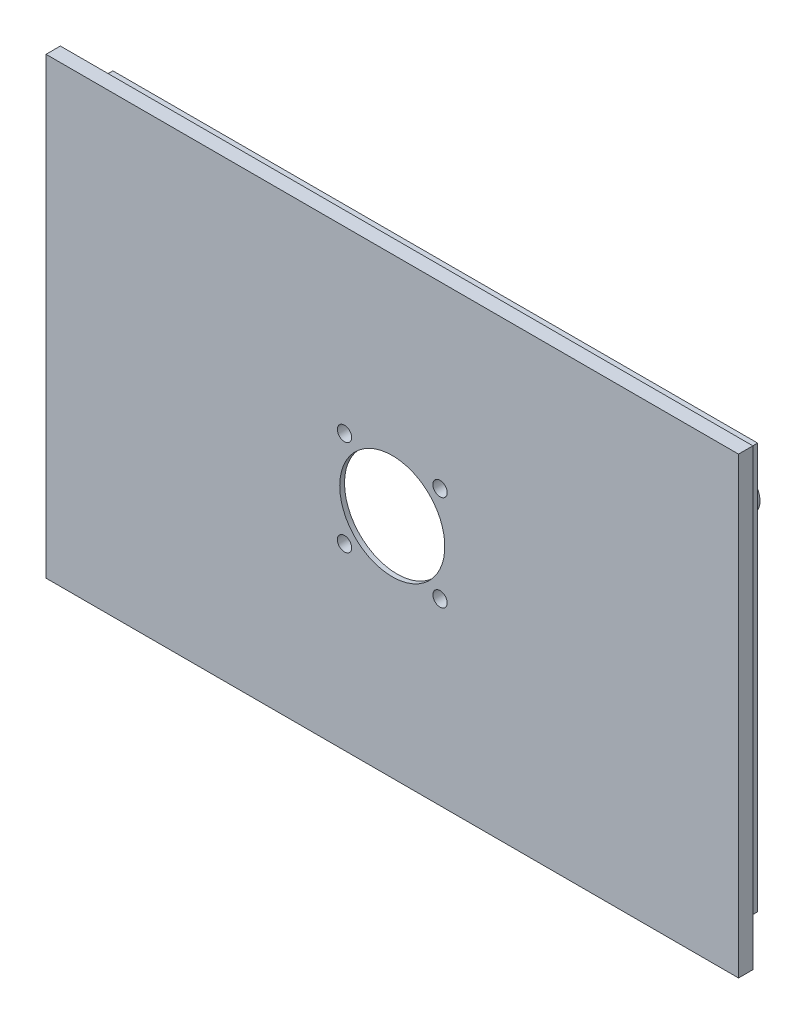
SolidWorks part; units mm, degrees
ref_plane "Plano frontal" through (0, 0, 0) normal (0, 0, 1) x (1, 0, 0)
ref_plane "Plano superior" through (0, 0, 0) normal (0, 1, 0) x (1, 0, 0)
ref_plane "Plano direito" through (0, 0, 0) normal (1, 0, 0) x (0, 0, -1)
sketch "Esboço1" plane through (0, 0, 0) normal (0, 0, 1) x (1, 0, 0)
  line L1 (0, 0) -> (150, 0)
  line L2 (0, 0) -> (0, 100)
  line L3 (0, 100) -> (150, 100)
  line L4 (150, 0) -> (150, 100)
  line L5 (10, 90) -> (140, 90)
  line L6 (10, 90) -> (10, 10)
  line L7 (10, 10) -> (140, 10)
  line L8 (140, 90) -> (140, 10)
  line L9 (7.5, 92.5) -> (142.5, 92.5)
  line L10 (7.5, 92.5) -> (7.5, 7.5)
  line L11 (7.5, 7.5) -> (142.5, 7.5)
  line L12 (142.5, 92.5) -> (142.5, 7.5)
  dimension "D1" = 100
  dimension "D2" = 150
  dimension "D3" = 130
  dimension "D4" = 80
  dimension "D5" = 10
  dimension "D6" = 10
  dimension "D7" = 2.5
  dimension "D8" = 2.5
  dimension "D9" = 2.5
  dimension "D10" = 2.5
extrude "Ressalto-extrusão1" add sketch "Esboço1" along normal blind 3 contours L3 L4 L1 L2
extrude "Ressalto-extrusão2" add sketch "Esboço1<3>" against normal blind 6 contours L12 L9 L10 L11 L5 L8 L7 L6 region at (75, 90.9047, 0)
sketch "Esboço1<3>" plane through (0, 0, 0) normal (0, 0, 1) x (1, 0, 0) same geometry as "Esboço1"
sketch "Esboço2" plane through (0, 0, 0) normal (0, 0, -1) x (-1, 0, 0)
  line L0 (-10, 90) -> (-140, 90) construction
  line L2 (-140, 90) -> (-140, 10) construction
  circle A0 centre (-130, 73.25) radius 4
  circle A1 centre (-32, 76.75) radius 4
  circle A2 centre (-28, 25.75) radius 4
  circle A3 centre (-124, 23.25) radius 4
  dimension "D6" = 50
  dimension "D7" = 8
  dimension "D8" = 8
  dimension "D9" = 8
  dimension "D10" = 8
  dimension "D1" = 98
  dimension "D2" = 3.5
  dimension "D3" = 4
  dimension "D4" = 6
  dimension "D5" = 51
  dimension "D11" = 13.25
  dimension "D12" = 10
extrude "Ressalto-extrusão3" add sketch "Esboço2" along normal blind 15
sketch "Esboço3" plane through (0, 0, -15) normal (0, 0, -1) x (-1, 0, 0)
  circle A0 centre (-130, 73.25) radius 1.75
  circle A1 centre (-32, 76.75) radius 1.75
  circle A2 centre (-28, 25.75) radius 1.75
  circle A3 centre (-124, 23.25) radius 1.75
  dimension "D1" = 3.5
  dimension "D2" = 3.5
  dimension "D3" = 3.5
  dimension "D4" = 3.5
extrude "Corte-extrusão1" cut sketch "Esboço3" against normal blind 8
sketch "Esboço4" plane through (0, 0, 0) normal (0, 0, -1) x (-1, 0, 0)
  line L0 (-75, 10) -> (-75, 100) construction
  line L1 (-68, 83.7797) -> (-82, 83.7797)
  line L2 (-68, 83.7797) -> (-68, 85.7604)
  line L3 (-68, 85.7604) -> (-82, 85.7604)
  line L4 (-82, 83.7797) -> (-82, 85.7604)
  line L5 (-10, 10) -> (-140, 10) construction
  line L6 (0, 100) -> (-150, 100) construction
  dimension "D1" = 7
  dimension "D2" = 7
extrude "Ressalto-extrusão4" add sketch "Esboço4" along normal blind 2
sketch "Esboço5" plane through (0, 0, 0) normal (0, 0, -1) x (-1, 0, 0)
  line L0 (-75, 50) -> (-75, 62.3582) construction
  line L1 (-86.5, 38.5) -> (-63.5, 38.5) construction
  line L2 (-86.5, 38.5) -> (-86.5, 61.5) construction
  line L3 (-86.5, 61.5) -> (-63.5, 61.5) construction
  line L4 (-63.5, 38.5) -> (-63.5, 61.5) construction
  line L5 (-86.5, 38.5) -> (-63.5, 61.5) construction
  line L6 (-86.5, 61.5) -> (-63.5, 38.5) construction
  line L7 (-75, 10) -> (-75, 90) construction
  line L8 (-10, 10) -> (-140, 10) construction
  line L9 (-10, 90) -> (-140, 90) construction
  line L10 (-10, 50) -> (-142.5, 50) construction
  line L11 (-10, 90) -> (-10, 10) construction
  line L12 (-142.5, 92.5) -> (-142.5, 7.5) construction
  circle A0 centre (-75, 50) radius 11
  circle A1 centre (-85, 60) radius 1.5
  circle A2 centre (-65, 40) radius 1.5
  circle A3 centre (-85, 40) radius 1.5
  circle A4 centre (-65, 60) radius 1.5
  point P27 (-75, 50)
extrude "Corte-extrusão2" cut sketch "Esboço5" against normal blind 10
chamfer "Chanfro1" distance 2 angle 56 1 edges at (64, 50, 0) first distance on face at (64, 50, 0)
sketch "Esboço6" plane through (0, 0, 0) normal (0, 0, -1) x (-1, 0, 0)
  line L1 (-147.5, 97.5) -> (-2.5, 97.5)
  line L2 (-147.5, 97.5) -> (-147.5, 2.5)
  line L3 (-147.5, 2.5) -> (-2.5, 2.5)
  line L4 (-2.5, 97.5) -> (-2.5, 2.5)
  line L5 (-150, 100) -> (0, 100)
  line L6 (-150, 100) -> (-150, 0)
  line L7 (-150, 0) -> (0, 0)
  line L8 (0, 100) -> (0, 0)
extrude "Corte-extrusão3" cut sketch "Esboço6" against normal blind 10
